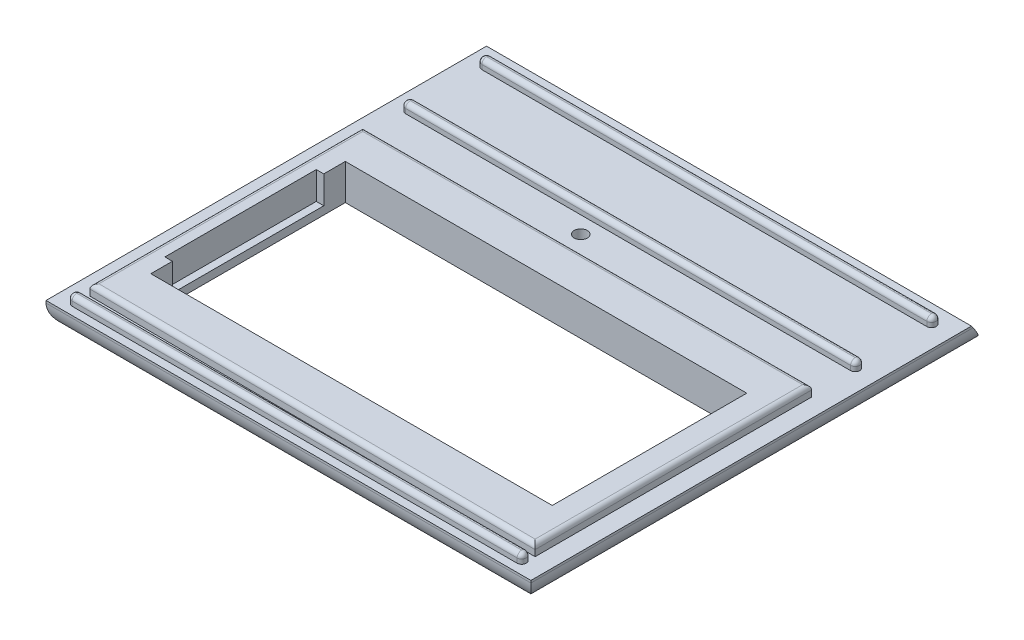
SolidWorks part; units mm, degrees
note: The reader was unsure of these and kept them because the rebuilt part matched: shared geometry of "Sketch1<4>".
ref_plane "Front Plane" through (0, 0, 0) normal (0, 0, 1) x (1, 0, 0)
ref_plane "Top Plane" through (0, 0, 0) normal (0, 1, 0) x (1, 0, 0)
ref_plane "Right Plane" through (0, 0, 0) normal (1, 0, 0) x (0, 0, -1)
sketch "Sketch1" plane through (0, 0, 0) normal (0, 1, 0) x (1, 0, 0)
  line L8 (-28.2204, -35.6927) -> (60.0796, -35.6927)
  line L10 (-28.2204, -35.6927) -> (-28.2204, 7.0873)
  line L12 (-28.2204, 7.0873) -> (60.0796, 7.0873)
  line L14 (60.0796, -35.6927) -> (60.0796, 7.0873)
  line L17 (65.6013, -44.9966) -> (-33.0054, -44.3077)
  line L18 (69.6573, 33.2233) -> (69.6573, -49.9652) construction
  line L19 (69.6573, 33.2233) -> (69.6573, -49.9652)
  line L20 (65.6013, 15.8535) -> (65.6013, -44.9966) construction
  line L21 (65.6013, 15.8535) -> (65.6013, -44.9966)
  line L23 (-33.0054, 15.7023) -> (65.6013, 15.8535)
  line L27 (-33.0054, -44.3077) -> (-33.0054, 15.7023) construction
  line L28 (-33.0054, -44.3077) -> (-33.0054, 15.7023)
  line L29 (-37.0054, -49.9652) -> (69.6573, -49.9652)
  line L30 (69.6573, 33.2233) -> (-37.0054, 33.2233)
  line L32 (-37.0054, -49.9652) -> (-37.0054, 33.2233)
extrude "Boss-Extrude1" add sketch "Sketch1" along normal blind 4
extrude "Boss-Extrude2" add sketch "Sketch1<4>" along a picked direction on the side of the normal offset from surface (6.35 mm away) 2.35
sketch "Sketch1<4>" plane through (0, 0, 0) normal (0, 1, 0) x (1, 0, 0) same geometry as "Sketch1"
sketch "Sketch2" plane through (0, 0, 0) normal (0, -1, 0) x (1, 0, 0)
  circle A1 centre (9.1926, -21.4502) radius 1.4494
extrude "Cut-Extrude1" cut sketch "Sketch2" against normal through all
sketch "Sketch3" plane through (-37.0054, 0, 0) normal (-1, 0, 0) x (0, 0, 1)
  line L0 (-32.8323, 0) -> (-49.7323, 0)
  line L1 (-32.8323, 4) -> (-46.9323, 4)
  line L2 (-46.9323, 4) -> (-49.7323, 0)
  line L3 (-32.8323, 4) -> (-32.8323, 0)
extrude "Boss-Extrude3" add sketch "Sketch3" against normal up to surface (106.6627 mm away) up to face at (69.6573, 2, 8.3709)
fillet "Fillet6" radius 1 4 edges at (-33.0054, 6.35, 14.3027) (16.298, 6.35, -15.7779) (65.6013, 6.35, 14.5715) (16.298, 6.35, 44.6522)
sketch "Sketch4" plane through (0, 4, 0) normal (0, 1, 0) x (1, 0, 0)
  line L0 (64.8646, 25.1529) -> (-33.0054, 25.1529)
  line L2 (64.8646, 27.1529) -> (-33.0054, 27.1529)
  line L3 (-33.0054, 41.9323) -> (64.8646, 41.9323)
  line L6 (64.8646, -48.2077) -> (-33.0054, -48.2077)
  line L7 (64.8646, -46.2077) -> (-33.0054, -46.2077)
  line L10 (64.8646, 43.9323) -> (-33.0054, 43.9323)
  arc A1 (64.8646, -48.2077) -> (64.8646, -46.2077) centre (64.8646, -47.2077) ccw
  arc A2 (-33.0054, -46.2077) -> (-33.0054, -48.2077) centre (-33.0054, -47.2077) ccw
  arc A3 (64.8646, 25.1529) -> (64.8646, 27.1529) centre (64.8646, 26.1529) ccw
  arc A4 (64.8646, 41.9323) -> (64.8646, 43.9323) centre (64.8646, 42.9323) ccw
  arc A5 (-33.0054, 43.9323) -> (-33.0054, 41.9323) centre (-33.0054, 42.9323) ccw
  arc A6 (-33.0054, 27.1529) -> (-33.0054, 25.1529) centre (-33.0054, 26.1529) ccw
extrude "Boss-Extrude4" add sketch "Sketch4" along normal blind 2
fillet "Fillet7" radius 1 12 edges at (15.9296, 6, 48.2077) (-34.0054, 6, 47.2077) (15.9296, 6, 46.2077) (65.8646, 6, 47.2077) (15.9296, 6, -25.1529) (-34.0054, 6, -26.1529) (15.9296, 6, -27.1529) (65.8646, 6, -26.1529) (15.9296, 6, -43.9323) (65.8646, 6, -42.9323) (15.9296, 6, -41.9323) (-34.0054, 6, -42.9323)
sketch "Sketch5" plane through (0, 6.35, 0) normal (0, 1, 0) x (1, 0, 0)
  line L2 (-28.2204, -30.9527) -> (-28.2204, 2.3473)
  line L3 (-28.2204, -30.9527) -> (-29.8704, -30.9527)
  line L4 (-29.8704, -30.9527) -> (-29.8704, 2.3473)
  line L5 (-29.8704, 2.3473) -> (-28.2204, 2.3473)
extrude "Cut-Extrude3" cut sketch "Sketch5" against normal offset from surface (6.08 mm away) 3.73 up to face at (16.326, 4, 1.5165)
sketch "Sketch10" plane through (0, 0, 0) normal (0, -1, 0) x (1, 0, 0)
  line L0 (-28.2204, 35.6927) -> (-28.2204, -7.0873) construction
  line L1 (-28.2204, 35.6927) -> (-28.2204, -7.0873)
  line L2 (-28.2204, -7.0873) -> (60.0796, -7.0873) construction
  line L3 (-28.2204, -7.0873) -> (60.0796, -7.0873)
  line L4 (-37.0054, 49.9652) -> (-37.0054, -49.7323)
  line L5 (-37.0054, -49.7323) -> (69.6573, -49.7323)
  line L6 (69.6573, -49.7323) -> (69.6573, 49.9652)
  line L7 (69.6573, 49.9652) -> (-37.0054, 49.9652)
  line L8 (-37.0054, 49.9652) -> (-37.0054, -43.0969)
  line L10 (69.6573, -43.0969) -> (69.6573, 49.9652)
  line L11 (69.6573, 49.9652) -> (-37.0054, 49.9652)
  line L12 (60.0796, 35.6927) -> (60.0796, -7.0873) construction
  line L13 (60.0796, 35.6927) -> (60.0796, -7.0873)
  line L14 (-37.0054, -43.0969) -> (69.6573, -43.0969)
  circle A0 centre (9.1926, -21.4502) radius 1.4494 construction
  circle A1 centre (9.1926, -21.4502) radius 1.4494
  circle M5 centre (9.1926, -21.4502) radius 1.4494
  line M6 (-37.0054, 49.9652) -> (-37.0054, -49.7323)
  line M8 (69.6573, -49.7323) -> (69.6573, 49.9652)
  line M9 (69.6573, 49.9652) -> (-37.0054, 49.9652)
  line M10 (60.0796, 35.6927) -> (60.0796, -7.0873)
  line M11 (60.0796, -7.0873) -> (-28.2204, -7.0873)
  line M12 (-28.2204, -7.0873) -> (-28.2204, 35.6927)
  line M13 (-28.2204, 35.6927) -> (60.0796, 35.6927)
  dimension "D1" = 0
extrude "Boss-Extrude6" add sketch "Sketch10" along normal blind 1.5 contours L14 M6 M8 M9 M13 M10 M11 M12 M5
sketch "Sketch11" plane through (-37.0054, 0, 0) normal (-1, 0, 0) x (0, 0, 1)
  line L2 (-49.7323, 0) -> (-50.7823, -1.5)
  line L4 (-43.0969, -1.5) -> (-50.7823, -1.5)
  line L5 (-43.0969, 0) -> (-49.7323, 0) construction
  line L6 (-43.0969, -1.5) -> (-43.0969, 0) construction
  line L7 (-43.0969, 0) -> (-49.7323, 0)
  line L8 (-43.0969, -1.5) -> (-43.0969, 0)
extrude "Boss-Extrude7" add sketch "Sketch11" against normal up to surface (106.6627 mm away) up to face at (69.6573, 0.8333, -13.8213)
fillet "Fillet9" radius 1 1 edges at (9.1926, -1.5, -22.8996)
fillet "Fillet10" radius 5 3 edges at (-37.0054, -1.5, -0.4085) (69.6573, -1.5, -0.4085) (16.326, -1.5, 49.9652)
